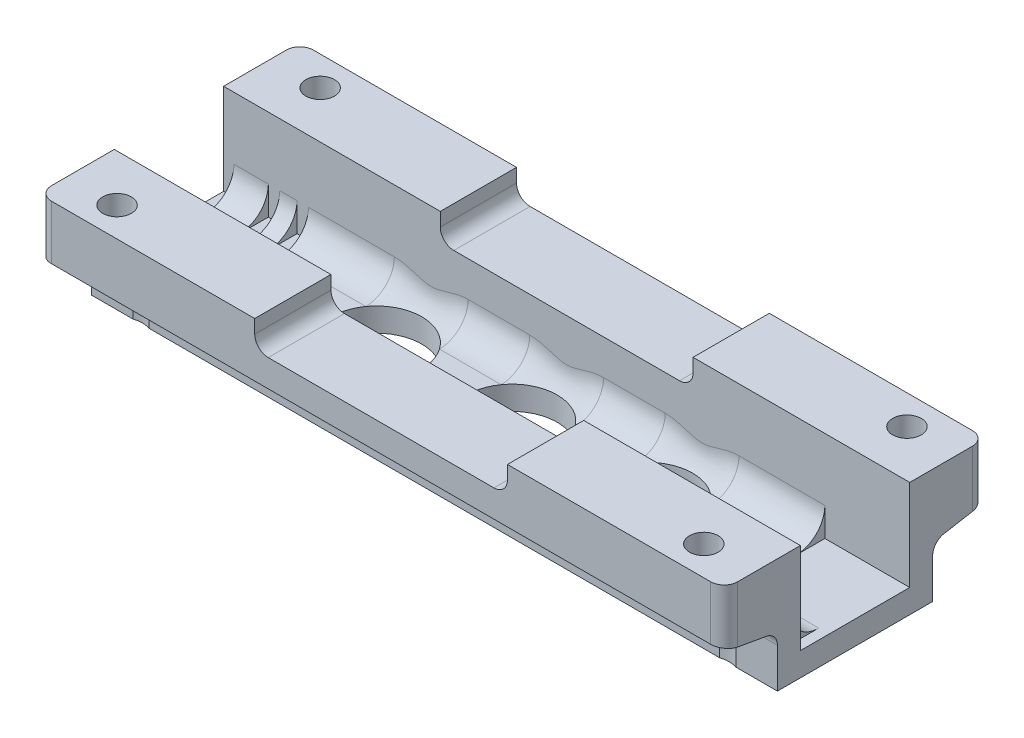
SolidWorks part; units mm, degrees
ref_plane "Front Plane" through (0, 0, 0) normal (0, 0, 1) x (1, 0, 0)
ref_plane "Top Plane" through (0, 0, 0) normal (0, 1, 0) x (1, 0, 0)
ref_plane "Right Plane" through (0, 0, 0) normal (1, 0, 0) x (0, 0, -1)
sketch "Sketch1" plane through (0, 0, 0) normal (1, 0, 0) x (0, 0, -1)
  line L0 (-14.5, 0) -> (-6.056, 0)
  line L1 (-14.5, 0) -> (-14.5, -6)
  line L2 (-14.5, -6) -> (-8.596, -7.041)
  line L3 (-8.596, -7.041) -> (-8.596, -12.7)
  line L4 (-8.596, -12.7) -> (8.596, -12.7)
  line L5 (8.596, -12.7) -> (8.596, -7.041)
  line L6 (8.596, -7.041) -> (14.5, -6)
  line L7 (14.5, -6) -> (14.5, 0)
  line L8 (-6.056, 0) -> (-6.056, -10.08)
  line L9 (-6.056, -10.08) -> (6.056, -10.08)
  line L10 (6.056, -10.08) -> (6.056, 0)
  line L11 (6.056, 0) -> (14.5, 0)
  point P4 (0, 0)
  point P10 (0, -12.7)
  point P16 (0, -10.08)
  dimension "D1" = 29
  dimension "D2" = 10
  dimension "D3" = 12.7
  dimension "D4" = 10.08
  dimension "D5" = 2.54
  dimension "D6" = 6
  dimension "D7" = 12.112
extrude "Boss-Extrude1" add sketch "Sketch1" along normal mid plane 76
sketch "Sketch8" plane through (0, 0, 0) normal (0, 1, 0) x (1, 0, 0)
  line L1 (-14, -14.5) -> (14, -14.5)
  line L2 (-14, -14.5) -> (-14, 14.5)
  line L3 (-14, 14.5) -> (14, 14.5)
  line L4 (14, -14.5) -> (14, 14.5)
  line L5 (-14, -14.5) -> (14, 14.5) construction
  line L6 (-14, 14.5) -> (14, -14.5) construction
  line L7 (38, -14.5) -> (-38, -14.5) construction
  line L8 (38, 14.5) -> (-38, 14.5) construction
  point P0 (0, 0)
  point P9 (0, 0)
  dimension "D1" = 28
extrude "Cut-Extrude5" cut sketch "Sketch8" against normal blind 3
sketch "Sketch7" plane through (0, -10.08, 0) normal (0, 1, 0) x (1, 0, 0)
  circle A0 centre (0, 0) radius 5
  dimension "D1" = 10
extrude "Cut-Extrude4" cut sketch "Sketch7" against normal through all
pattern_linear "LPattern1" count 2 spacing 15 along (-1, 0, 0) of "Cut-Extrude4"
fillet "Fillet2" radius 1.5 10 edges at (-38, -3, -14.5) (-38, -3, 14.5) (38, -3, -14.5) (38, -3, 14.5) (0, -7.041, 8.596) (0, -7.041, -8.596) (-14, -3, 10.278) (14, -3, 10.278) (14, -3, -10.278) (-14, -3, -10.278)
sketch "Sketch2" plane through (0, 0, 0) normal (0, -1, 0) x (-1, 0, 0)
  line L0 (32.5, -11.25) -> (32.5, 11.25) construction
  line L1 (38, -8.596) -> (38, 8.596) construction
  circle A0 centre (32.5, -11.25) radius 2.8
  circle A1 centre (32.5, 11.25) radius 2.8
  point P4 (32.5, 0)
  dimension "D1" = 5.6
  dimension "D2" = 22.5
  dimension "D3" = 5.5
extrude "Cut-Extrude1" cut sketch "Sketch2" along normal through all from offset 4.5
sketch "Sketch3" plane through (0, -4.5, 0) normal (0, -1, 0) x (-1, 0, 0)
  circle A0 centre (32.5, -11.25) radius 1.5875
  circle A1 centre (32.5, 11.25) radius 1.5875
  point P6 (34, 11.2225)
  dimension "D1" = 3.175
extrude "Cut-Extrude2" cut sketch "Sketch3" against normal through all
mirror "Mirror1" about plane through (0, 0, 0) normal (1, 0, 0) of "LPattern1", "Cut-Extrude1", "Cut-Extrude2"
fillet "Fillet1" radius 3.175 2 edges at (0, -10.08, -6.056) (0, -10.08, 6.056)
sketch "Sketch4" plane through (0, 0, 0) normal (0, 1, 0) x (1, 0, 0)
  line L0 (38, -6.056) -> (14, -6.056) construction
  line L1 (-38, 6.056) -> (-36.857, 6.056)
  line L2 (-38, 6.056) -> (-38, -6.056)
  line L3 (-38, -6.056) -> (-28.602, -6.056)
  line L4 (-36.857, 6.056) -> (-36.857, 0)
  line L5 (-38, 6.056) -> (-19.0865, 6.056) construction
  line L6 (-33.047, 6.056) -> (-31.777, 6.056)
  line L7 (-33.047, 6.056) -> (-33.047, 0)
  line L9 (-31.777, 6.056) -> (-31.777, 0)
  line L10 (38, -6.056) -> (19.0865, -6.056) construction
  line L11 (-29.872, 6.056) -> (-28.602, 6.056)
  line L12 (-29.872, 6.056) -> (-29.872, 0)
  line L14 (-28.602, 6.056) -> (-28.602, -6.056)
  line L16 (-36.857, 0) -> (-33.047, 0)
  line L17 (-31.777, 0) -> (-29.872, 0)
  point P22 (-31.777, 3.028)
  dimension "D1" = 1.143
  dimension "D2" = 1.27
  dimension "D3" = 3.81
  dimension "D4" = 1.905
extrude "Cut-Extrude3" cut sketch "Sketch4" against normal up to surface (10.08 mm away) up to face at (28.7716, -10.08, 0)
ref_axis "Axis1" through (0, -13.335, 0) along (0, 1, 0)
pattern_circular "CirPattern1" count 2 over 360 about axis through (0, -13.335, 0) along (0, 1, 0) of "Cut-Extrude3"
